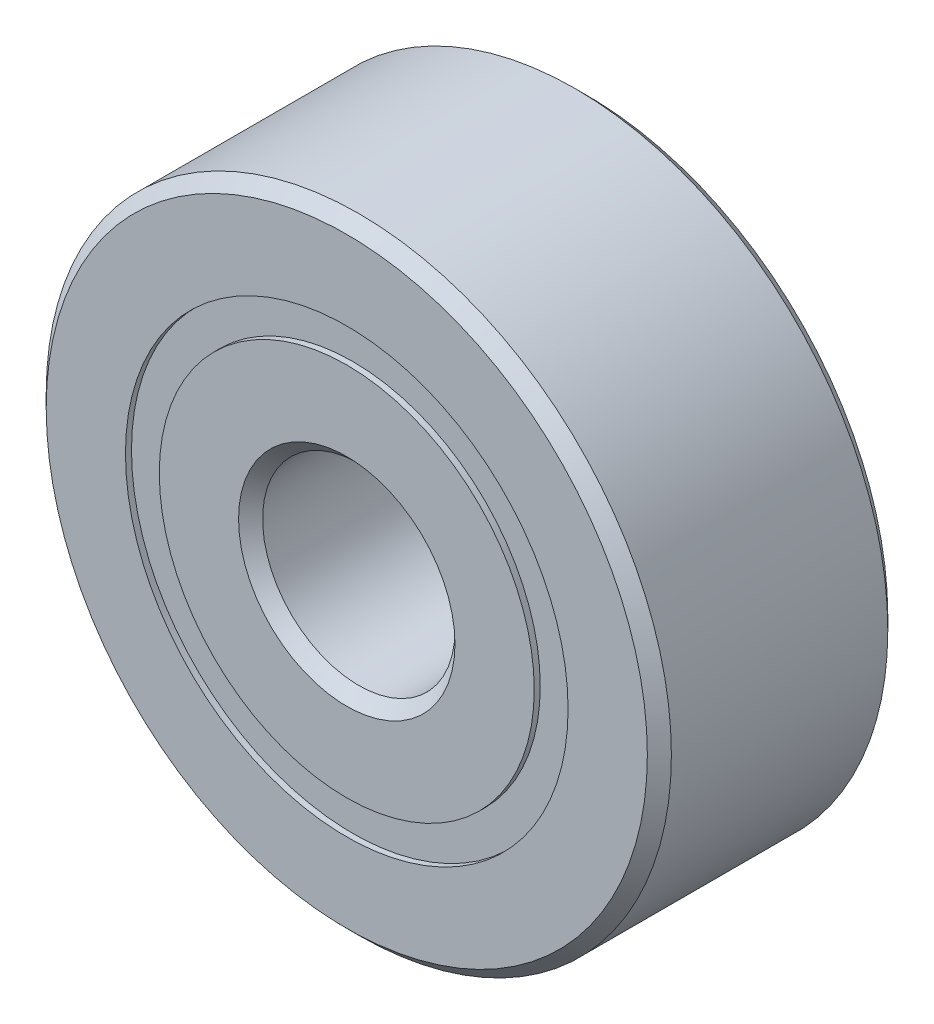
SolidWorks part; units mm, degrees
ref_plane "Front Plane" through (0, 0, 0) normal (0, 0, 1) x (1, 0, 0)
ref_plane "Top Plane" through (0, 0, 0) normal (0, 1, 0) x (1, 0, 0)
ref_plane "Right Plane" through (0, 0, 0) normal (1, 0, 0) x (0, 0, -1)
sketch "Sketch1" plane through (0, 0, 0) normal (1, 0, 0) x (0, 0, -1)
  line L0 (-2.5, 0) -> (2.5, 0) construction
  line L1 (0, 6.5) -> (0, -6.5) construction
  line L2 (2.25, 6.5) -> (-2.25, 6.5)
  line L3 (-2.25, 6.5) -> (-2.5, 6.25)
  line L4 (-2.5, 6.25) -> (-2.5, 4.6016)
  line L5 (-2.5, 4.6016) -> (-1.1111, 4.6016)
  line L6 (2.5, 4.6016) -> (1.1111, 4.6016)
  line L7 (2.5, 6.25) -> (2.5, 4.6016)
  line L8 (2.25, 6.5) -> (2.5, 6.25)
  line L9 (0, 6.5) -> (0, 4.25) construction
  line L10 (0, 4.25) -> (0, 2) construction
  arc A0 (-1.1111, 4.6016) -> (1.1111, 4.6016) centre (0, 4.25) cw
  point P14 (0, 2)
  dimension "Width" = 5
  dimension "OD" = 13
  dimension "D1" = 45
  dimension "D2" = 0.25
  dimension "Shaft Dia" = 4
  dimension "D3" = 2.2222
  dimension "D4" = 0.3516
revolve "Revolve1" add sketch "Sketch1" angle 360 about L0
sketch "Sketch3" plane through (0, 0, 0) normal (1, 0, 0) x (0, 0, -1)
  line L0 (-2.5, 3.8984) -> (-1.1111, 3.8984)
  line L1 (0, 6.5) -> (0, -6.5) construction
  line L2 (-2.5, 6.25) -> (-2.5, 4.6016) construction
  line L3 (-2.5, 3.8984) -> (-2.5, 2.25)
  line L4 (-2.25, 6.5) -> (-2.5, 6.25) construction
  line L5 (-2.5, 2.25) -> (-2.25, 2)
  line L6 (-2.25, 2) -> (2.25, 2)
  line L7 (2.25, 6.5) -> (2.25, -6.5) construction
  line L8 (2.25, 2) -> (2.5, 2.25)
  line L9 (2.5, -6.25) -> (2.5, 6.25) construction
  line L10 (2.5, 2.25) -> (2.5, 3.8984)
  line L11 (2.5, 3.8984) -> (1.1111, 3.8984)
  line L13 (2.25, 6.5) -> (2.5, 6.25) construction
  arc A0 (1.1111, 4.6016) -> (-1.1111, 4.6016) centre (0, 4.25) ccw construction
  arc A1 (1.1111, 3.8984) -> (-1.1111, 3.8984) centre (0, 4.25) cw
revolve "Revolve3" add sketch "Sketch3" angle 360 about L0
sketch "Sketch4" plane through (0, 0, 0) normal (1, 0, 0) x (0, 0, -1)
  line L0 (-1.1654, 4.25) -> (1.1654, 4.25)
  arc A2 (-1.1654, 4.25) -> (1.1654, 4.25) centre (0, 4.25) cw
  arc A3 (1.1111, 4.6016) -> (-1.1111, 4.6016) centre (0, 4.25) ccw construction
revolve "Revolve4" add sketch "Sketch4" angle 360 about L0
ref_axis "Axis1" through (0, 0, -2.5) along (0, 0, 1)
pattern_circular "CirPattern1" count 12 every 30 about axis through (0, 0, -2.5) along (0, 0, 1) of bodies 104
sketch "Sketch5" plane through (0, 0, 0) normal (1, 0, 0) x (0, 0, -1)
  line L0 (-2.5, 4.6016) -> (-1.1111, 4.6016) construction
  line L1 (-2.375, 4.6016) -> (-1.1654, 4.6016)
  line L2 (-2.375, 4.6016) -> (-2.375, 3.8984)
  line L3 (-2.375, 3.8984) -> (-1.1654, 3.8984)
  line L4 (-1.1654, 4.6016) -> (-1.1654, 3.8984)
  line L5 (-2.5, 3.8984) -> (-1.1111, 3.8984) construction
  line L6 (2.5, 4.6016) -> (1.1111, 4.6016) construction
  line L7 (2.375, 4.6016) -> (1.1654, 4.6016)
  line L8 (2.375, 4.6016) -> (2.375, 3.8984)
  line L9 (2.375, 3.8984) -> (1.1654, 3.8984)
  line L10 (1.1654, 4.6016) -> (1.1654, 3.8984)
  line L11 (2.5, 3.8984) -> (1.1111, 3.8984) construction
  line L12 (-2.25, 6.5) -> (-2.5, 6.25) construction
  point P18 (-2.375, 6.375)
revolve "Revolve5" add sketch "Sketch5" angle 360 about L0
sketch "Sketch6" plane through (0, 0, 0) normal (1, 0, 0) x (0, 0, -1)
  line L0 (2.5, 0) -> (-2.5, 0) construction
  line L1 (2.5, 4.6016) -> (1.4, 4.6016)
  line L2 (2.5, 4.6016) -> (2.5, 9.5)
  line L3 (2.5, 9.5) -> (1.4, 9.5)
  line L4 (1.4, 4.6016) -> (1.4, 9.5)
  dimension "Th" = 1.1
  dimension "Flange OD" = 19
revolve "Revolve6" [suppressed] add sketch "Sketch6" angle 360 about L0
equation "\"D2@Sketch1\" = \"Width@Sketch1\"*.05"
equation "\"D3@Sketch1\" = \"Width@Sketch1\"/2.25"
equation "\"D4@Sketch1\" = (((\"OD@Sketch1\"-\"Width@Sketch1\")/2)/3.25)/3.5"
equation "\"D2@CirPattern1\" = 360/\"Balls@CirPattern1\""
